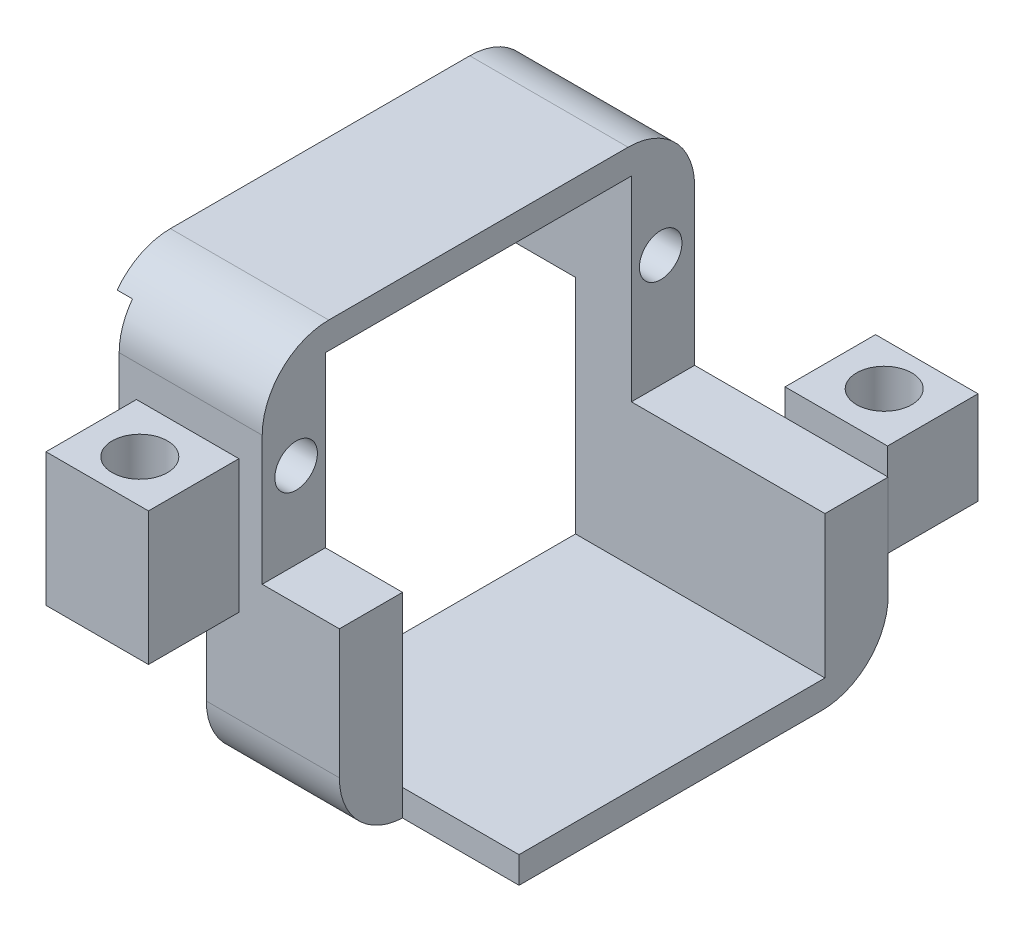
SolidWorks part; units mm, degrees
ref_plane "Front Plane" through (0, 0, 0) normal (0, 0, 1) x (1, 0, 0)
ref_plane "Top Plane" through (0, 0, 0) normal (0, 1, 0) x (1, 0, 0)
ref_plane "Right Plane" through (0, 0, 0) normal (1, 0, 0) x (0, 0, -1)
sketch "Sketch1" plane through (0, 0, 0) normal (0, 1, 0) x (1, 0, 0)
  line L0 (-1.1, 16.25) -> (-1.1, 11.5)
  line L1 (-17.65, -16.25) -> (17.65, -16.25)
  line L2 (-17.65, -16.25) -> (-17.65, 16.25)
  line L3 (-17.65, 16.25) -> (17.65, 16.25)
  line L4 (17.65, -16.25) -> (17.65, 16.25)
  line L5 (-17.65, -16.25) -> (17.65, 16.25) construction
  line L6 (-17.65, 16.25) -> (17.65, -16.25) construction
  line L7 (-1.1, 11.5) -> (17.65, 11.5)
  line L8 (-1.1, -16.25) -> (-1.1, -11.5)
  line L9 (-1.1, -11.5) -> (17.65, -11.5)
  line L10 (-1.1, 11.5) -> (-1.1, -11.5) construction
  line L11 (8.9, -11.5) -> (8.9, -16.25)
  line L12 (-8.8, 16.25) -> (-8.8, 11.5)
  line L13 (-8.8, 11.5) -> (-3.8, 11.5)
  line L14 (-3.8, 11.5) -> (-3.8, 16.25)
  line L15 (-3.8, -16.25) -> (-3.8, -11.5)
  line L16 (-3.8, -11.5) -> (-8.8, -11.5)
  line L17 (-8.8, -11.5) -> (-8.8, -16.25)
  line L18 (-8.8, 11.5) -> (-8.8, -11.5)
  line L19 (17.6, 16.25) -> (17.6, 23.05)
  line L20 (17.6, 23.05) -> (9.9, 23.05)
  line L21 (9.9, 23.05) -> (9.9, 16.25)
  line L22 (-6.35, -16.25) -> (-6.35, -23.05)
  line L23 (-6.35, -23.05) -> (1.35, -23.05)
  line L24 (1.35, -23.05) -> (1.35, -16.25)
  line L28 (-1.1, 11.5) -> (-1.1, -11.5)
  circle A0 centre (13.75, 19.85) radius 2.075
  circle A2 centre (-2.5, -19.85) radius 2.075
  point P0 (0, 0)
  point P11 (-1.1, 0)
  point P30 (0, 0)
  point P31 (13.75, 23.05)
  point P34 (0, 0)
  point P36 (0, 0)
  point P37 (0, 0)
  point P38 (0, 0)
  point P45 (-2.5, -23.05)
  dimension "D11" = 4.15
  dimension "D19" = 4.15
  dimension "D1" = 32.5
  dimension "D2" = 23
  dimension "D3" = 8.75
  dimension "D4" = 10
  dimension "D5" = 16.55
  dimension "D6" = 2.7
  dimension "D7" = 5
  dimension "D8" = 13.75
  dimension "D9" = 7.7
  dimension "D10" = 6.8
  dimension "D12" = 2.5
  dimension "D13" = 19.85
  dimension "D16" = 7.7
  dimension "D17" = 6.8
  dimension "D20" = 19.85
extrude "Boss-Extrude1" add sketch "Sketch1" against normal blind 2 contours L7 L28 L9 L4 | L0 L7 L4 L3 | L11 L9 L8 L1 region at (8.275, 0, -13.875) region at (8.275, 0, 0) region at (3.9, 0, 13.875)
extrude "Boss-Extrude2" add sketch "Sketch1<3>" along normal blind 12.7 contours L0 L7 L4 L3 | L11 L9 L8 L1 region at (8.275, 0, -13.875) region at (3.9, 0, 13.875)
sketch "Sketch1<3>" plane through (0, 0, 0) normal (0, 1, 0) x (1, 0, 0) same geometry as "Sketch1"
sketch "Sketch3" plane through (0, 0, 0) normal (0, 1, 0) x (1, 0, 0)
  line L0 (3.1, 16.25) -> (3.1, 11.5)
  line L1 (-17.65, 16.25) -> (17.65, 16.25) construction
  line L2 (-1.1, 11.5) -> (17.65, 11.5) construction
  line L3 (3.1, 11.5) -> (-17.65, 11.5)
  line L4 (-17.65, -16.25) -> (-17.65, 16.25) construction
  line L5 (3.1, -16.25) -> (3.1, -11.5)
  line L6 (-17.65, -16.25) -> (17.65, -16.25) construction
  line L7 (-1.1, -11.5) -> (17.65, -11.5) construction
  line L8 (3.1, -11.5) -> (-17.65, -11.5)
  line L9 (3.1, 11.5) -> (3.1, -11.5)
  line L10 (-7.65, -11.5) -> (-7.65, -16.275)
  line L11 (3.1, 16.25) -> (-17.65, 16.25)
  line L12 (-17.65, 16.25) -> (-17.65, 11.5)
  line L13 (-17.65, -11.5) -> (-17.65, -16.25)
  line L14 (-17.65, -16.25) -> (3.1, -16.25)
  line L15 (-8.8, 11.5) -> (-8.8, -11.5)
  line L16 (-8.8, 11.5) -> (-8.8, 16.25)
  line L17 (-8.8, -11.5) -> (-8.8, -16.25)
  dimension "D1" = 20.75
  dimension "D2" = 10
extrude "Boss-Extrude3" add sketch "Sketch3" along normal blind 12.7 from surface contours L11 L12 L3 L0 | L10 L14 L5 L8 region at (-2.85, 0, -13.875) region at (-2.275, 0, 13.875) starting at face at (8.275, 12.7, -13.875)
extrude "Boss-Extrude4" add sketch "Sketch3<3>" along normal blind 2 from surface contours L16 L3 L0 L11 | L3 L15 L8 L9 | L10 L14 L5 L8 | L8 L17 L14 L10 region at (-2.85, 0, -13.875) region at (-2.85, 0, 0) region at (-2.275, 0, 13.875) region at (-8.225, 0, 13.875) starting at face at (-2.275, 25.4, 13.875)
sketch "Sketch3<3>" plane through (0, 0, 0) normal (0, 1, 0) x (1, 0, 0) same geometry as "Sketch3"
sketch "Sketch2" plane through (0, 0, 0) normal (1, 0, 0) x (0, 0, -1)
  line L0 (13.7, 6.45) -> (-13.7, 6.45) construction
  line L1 (-13.7, 19.15) -> (13.7, 19.15) construction
  circle A0 centre (13.7, 6.45) radius 1.6
  circle A1 centre (-13.7, 6.45) radius 1.6
  circle A2 centre (-13.7, 19.15) radius 1.6
  circle A3 centre (13.7, 19.15) radius 1.6
  point P4 (0, 6.45)
  dimension "D1" = 3.2
  dimension "D2" = 3.2
  dimension "D6" = 3.2
  dimension "D7" = 3.2
  dimension "D3" = 27.4
  dimension "D4" = 6.45
  dimension "D5" = 6.45
extrude "Cut-Extrude1" cut sketch "Sketch2" along normal blind 8 from surface contours A1 | A0 region at (0, 6.45, -13.7) region at (0, 6.45, 13.7) starting at face at (-1.1, 5.85, 0)
extrude "Cut-Extrude2" cut sketch "Sketch2<3>" against normal blind 8 from surface contours A3 | A2 region at (0, 19.15, 13.7) region at (0, 19.15, -13.7) starting at face at (3.1, 19.55, 0)
sketch "Sketch2<3>" plane through (0, 0, 0) normal (1, 0, 0) x (0, 0, -1) same geometry as "Sketch2"
extrude "Boss-Extrude5" add sketch "Sketch1<4>" along normal blind 10 from offset 10 contours L23 L24 L1 L22 A2 region at (0.125, 0, 16.3527)
sketch "Sketch1<4>" plane through (0, 0, 0) normal (0, 1, 0) x (1, 0, 0) same geometry as "Sketch1"
extrude "Boss-Extrude6" add sketch "Sketch1<7>" against normal blind 7 from surface contours L20 L21 L3 L19 A0 region at (10.0027, 0, -19.65) starting at face at (10.375, 12.7, -13.875)
sketch "Sketch1<7>" plane through (0, 0, 0) normal (0, 1, 0) x (1, 0, 0) same geometry as "Sketch1"
fillet "Fillet1" radius 5 4 edges at (3.9, -2, 16.25) (-2.85, 27.4, 16.25) (8.275, -2, -16.25) (-2.85, 27.4, -16.25)
sketch "Sketch5" plane through (0, 0, 0) normal (0, 1, 0) x (1, 0, 0)
  line L1 (17.65, 16.25) -> (3.1, 16.25)
  line L2 (17.65, 16.25) -> (17.65, 11.5)
  line L3 (17.65, 11.5) -> (3.1, 11.5)
  line L4 (3.1, 16.25) -> (3.1, 11.5)
extrude "Cut-Extrude3" cut sketch "Sketch5" against normal blind 2 from surface starting at face at (12.0625, 12.7, -16.7625)
sketch "Sketch6" plane through (0, 0, 0) normal (0, 1, 0) x (1, 0, 0)
  line L1 (-8.8, 11.5) -> (-1.1, 11.5)
  line L2 (-8.8, 11.5) -> (-8.8, 16.25)
  line L3 (-8.8, 16.25) -> (-1.1, 16.25)
  line L4 (-1.1, 11.5) -> (-1.1, 16.25)
extrude "Cut-Extrude4" cut sketch "Sketch6" along normal blind 4 from surface starting at face at (-4.95, 12.7, -13.875)
